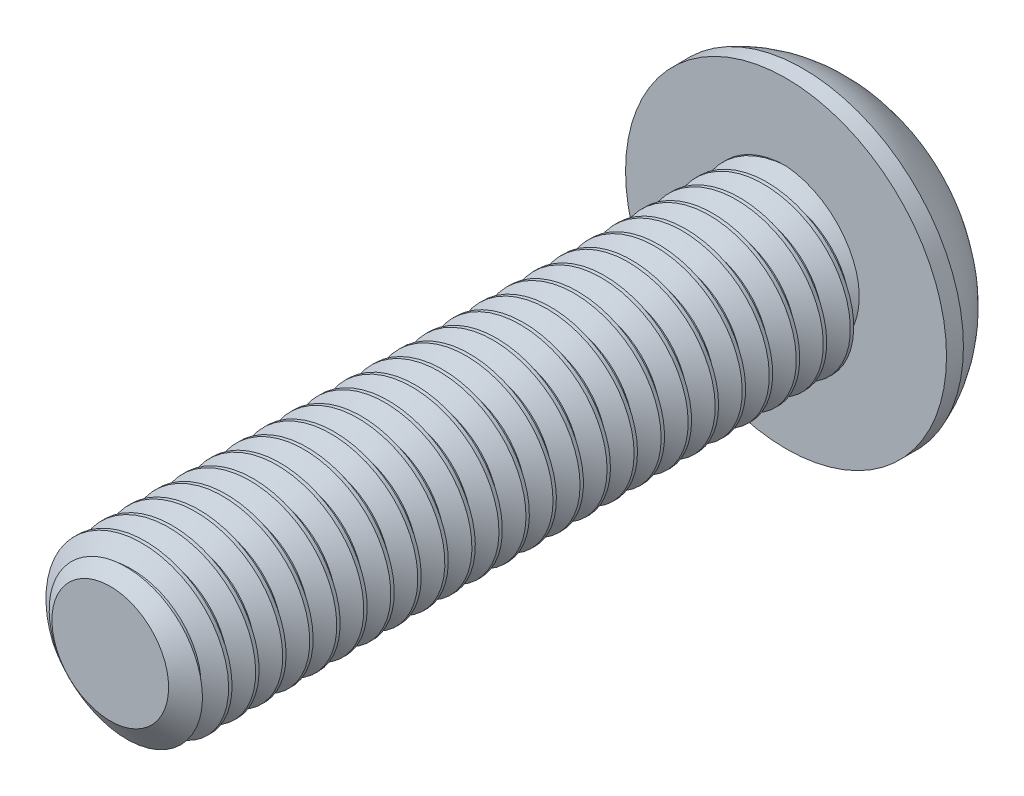
SolidWorks part; units mm, degrees
material "AISI 304"
ref_plane "Front Plane" through (0, 0, 0) normal (0, 0, 1) x (1, 0, 0)
ref_plane "Top Plane" through (0, 0, 0) normal (0, 1, 0) x (1, 0, 0)
ref_plane "Right Plane" through (0, 0, 0) normal (1, 0, 0) x (0, 0, -1)
sketch "Sketch1" plane through (0, 0, 0) normal (0, 0, 1) x (1, 0, 0)
  circle A0 centre (0, 0) radius 2.5
  dimension "OD" = 5
extrude "Extrude1" add sketch "Sketch1" against normal blind 20
sketch "Sketch2" plane through (0, 0, 0) normal (0, 0, 1) x (1, 0, 0)
  circle A0 centre (0, 0) radius 2.5 construction
  circle A1 centre (0, 0) radius 2.5
curve "Helix/Spiral1" pitch 0.8 height 20.8 turns 26 parameters "pitch"=0.8
sketch "Sketch3" plane through (0, 0, 0) normal (1, 0, 0) x (0, 0, -1)
  line L0 (-0.7, 2.5) -> (-0.4, 1.9804)
  line L1 (-0.4, 1.9804) -> (-0.3, 1.9804)
  line L2 (-0.3, 1.9804) -> (0, 2.5)
  line L3 (-0.7, 2.5) -> (0, 2.5)
  line L4 (-0.35, 2.5) -> (-0.35, 1.9804) construction
  line L5 (-0.55, 2.2402) -> (-0.15, 2.2402) construction
  line L6 (0, 2.5) -> (0, -2.5) construction
  dimension "D1" = 0.1
  dimension "D2" = 0.4
  dimension "D3" = 60
sweep "Cut-Sweep1" cut profiles "Sketch3" path "Helix/Spiral1"
sketch "Sketch4" plane through (0, 0, 0) normal (1, 0, 0) x (0, 0, -1)
  line L0 (0.5417, 2.5) -> (0, 1.7264)
  line L1 (0, 1.7264) -> (0, 2.5)
  line L2 (0.5417, 2.5) -> (0, 2.5)
  line L3 (-0.7, 2.5) -> (0, 2.5) construction
  line L4 (0, 0) -> (7.0209, 0) construction
  dimension "D1" = 55
  dimension "D2" = 0.254
revolve "Cut-Revolve1" cut sketch "Sketch4" angle 360 about L4
sketch "Sketch5" plane through (0, 0, 0) normal (1, 0, 0) x (0, 0, -1)
  line L0 (20, -1.991) -> (20, 1.7838) construction
  line L1 (20, 2.627) -> (28.1202, 2.627)
  line L2 (20, 2.627) -> (20, 0)
  line L3 (20, 0) -> (28, 0)
  line L4 (28, 2.2968) -> (28, 0)
  line L5 (28.1202, 2.627) -> (28, 2.2968)
  line L6 (0, 0) -> (9.9695, 0) construction
  point P3 (28, 2.627)
  point P10 (28, 2.627)
  dimension "D1" = 0.3302
  dimension "Thread min" = 28
  dimension "D2" = 0.127
  dimension "D3" = 20
revolve "partially thread" [suppressed] add sketch "Sketch5" angle 360 about L6
sketch "Sketch6" plane through (0, 0, -20) normal (0, 0, -1) x (-1, 0, 0)
  circle A0 centre (0, 0) radius 4.75
  dimension "head dia" = 9.5
extrude "Extrude2" add sketch "Sketch6" along normal blind 2.75
sketch "Sketch10" plane through (0, 0, 0) normal (1, 0, 0) x (0, 0, -1)
  line L0 (22.75, -4.75) -> (22.75, 4.75) construction
  line L1 (0, 0) -> (15.9584, 0) construction
  line L2 (22.75, 4.75) -> (20, 4.75) construction
  line L3 (20, 4.75) -> (20, -4.75) construction
  line L4 (20.5, 4.75) -> (20.5, 5.25)
  line L5 (20.5, 5.25) -> (23.25, 5.25)
  line L6 (23.25, 5.25) -> (23.25, 1.5)
  line L7 (22.75, 1.5) -> (23.25, 1.5)
  arc A0 (22.75, 1.5) -> (20.5, 4.75) centre (19.2778, 1.5) ccw
  dimension "D1" = 3
  dimension "D2" = 0.5
  dimension "D3" = 0.5
revolve "Cut-Revolve2" cut sketch "Sketch10" angle 360 about L1
ref_plane "Plane1" through (0, 0, -22.75) normal (0, 0, 1) x (1, 0, 0)
sketch "Sketch7" plane through (0, 0, -22.75) normal (0, 0, -1) x (-1, 0, 0)
  line L1 (0, 1.7321) -> (-1.5, 0.866)
  line L2 (-1.5, 0.866) -> (-1.5, -0.866)
  line L3 (-1.5, -0.866) -> (0, -1.7321)
  line L4 (0, -1.7321) -> (1.5, -0.866)
  line L5 (1.5, -0.866) -> (1.5, 0.866)
  line L6 (1.5, 0.866) -> (0, 1.7321)
  circle A0 centre (0, 0) radius 1.5 construction
  dimension "hex dia" = 3
extrude "Cut-Extrude1" cut sketch "Sketch7" against normal blind 2.25
sketch "Sketch8" plane through (0, 0, -22.75) normal (0, 0, 1) x (1, 0, 0)
  circle A0 centre (0, 0) radius 1.7321
extrude "Cut-Extrude2" cut sketch "Sketch8" along normal through all draft 45
sketch "Sketch9" plane through (0, 0, 0) normal (1, 0, 0) x (0, 0, -1)
  line L0 (0, 2.5) -> (0, -2.5) construction
  line L1 (4.4, 2.5) -> (4.4, -2.5) construction
  dimension "D1" = 4.4
  dimension "D4" = 0.635
  dimension "D5" = 0.3302
equation "\"D3@Helix/Spiral1\" = \"screw length@Extrude1\"+\"pitch@Helix/Spiral1\""
equation "\"D1@Sketch3\" = \"pitch@Helix/Spiral1\"*.125"
equation "\"D2@Sketch3\" = \"pitch@Helix/Spiral1\"*.5"
equation "\"D1@Cut-Extrude1\" = \"hex dia@Sketch7\"*.75"
equation "\"D1@Sketch9\" = \"pitch@Helix/Spiral1\"*5.5"
equation "\"D1@Sketch10\" = \"hex dia@Sketch7\""
equation "\"D1@Plane1\" = \"head depth@Extrude2\""
